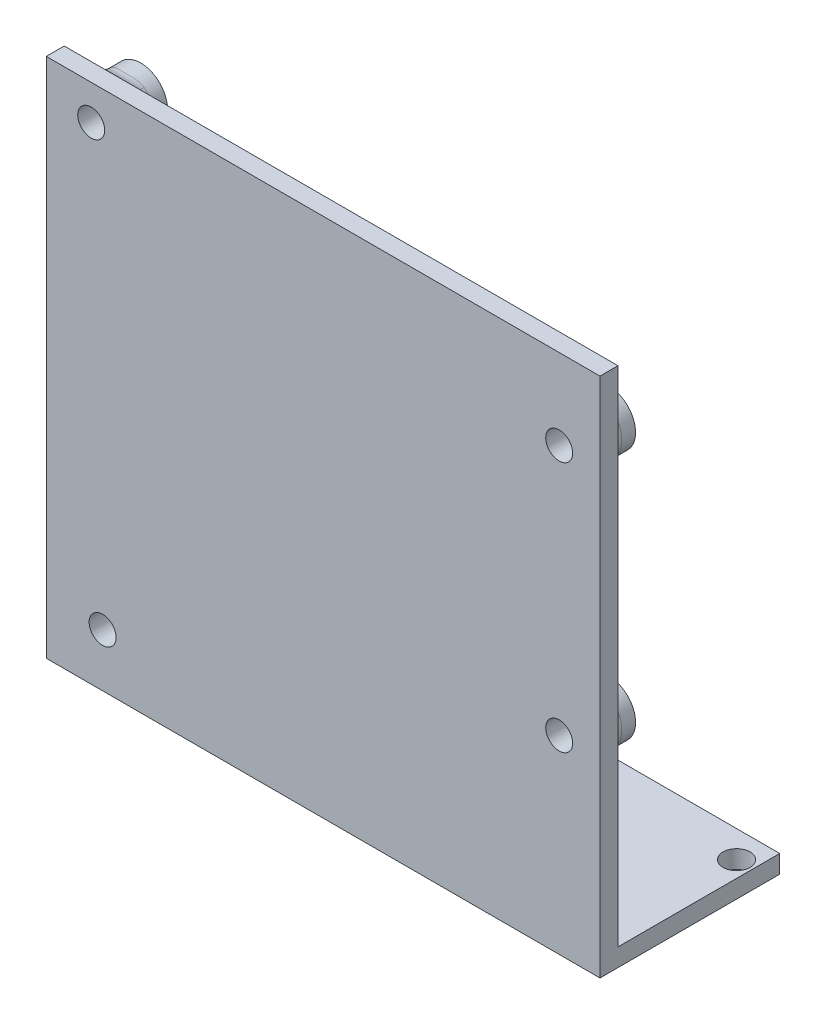
SolidWorks part; units mm, degrees
ref_plane "Piano frontale" through (0, 0, 0) normal (0, 0, 1) x (1, 0, 0)
ref_plane "Piano superiore" through (0, 0, 0) normal (0, 1, 0) x (1, 0, 0)
ref_plane "Piano destro" through (0, 0, 0) normal (1, 0, 0) x (0, 0, -1)
sketch "Schizzo1" plane through (0, 0, 0) normal (0, 0, 1) x (1, 0, 0)
  line L1 (87, 28) -> (-87, 28)
  line L2 (87, 28) -> (87, -28)
  line L3 (87, -28) -> (-87, -28)
  line L4 (-87, 28) -> (-87, -28)
  line L5 (87, 28) -> (-87, -28) construction
  line L6 (87, -28) -> (-87, 28) construction
  point P0 (0, 0)
  dimension "D1" = 56
  dimension "D2" = 174
extrude "Estrusione-Estrusione1" add sketch "Schizzo1" along normal blind 2
sketch "Schizzo4" plane through (0, 0, 0) normal (0, 0, -1) x (-1, 0, 0)
  line L0 (87, 0) -> (-87, 0) construction
  line L1 (87, 28) -> (87, -28) construction
  line L2 (-87, -28) -> (-87, 28) construction
  line L3 (83.5, 0) -> (83.5, -24.5) construction
  line L4 (83.5, -24.5) -> (25.5, -24.5) construction
  line L5 (83.5, 0) -> (83.5, 24.5) construction
  line L6 (83.5, 24.5) -> (25.5, 24.5) construction
  line L7 (25.5, 24.5) -> (25.5, -24.5) construction
  circle A0 centre (83.5, -24.5) radius 1.5
  circle A1 centre (25.5, -24.5) radius 1.5
  circle A2 centre (25.5, 24.5) radius 1.5
  circle A3 centre (83.5, 24.5) radius 1.5
  circle A4 centre (83.5, -24.5) radius 3
  circle A5 centre (25.5, -24.5) radius 3
  circle A6 centre (25.5, 24.5) radius 3
  circle A7 centre (83.5, 24.5) radius 3
  dimension "D5" = 3
  dimension "D6" = 3
  dimension "D7" = 3
  dimension "D8" = 3
  dimension "D9" = 6
  dimension "D10" = 6
  dimension "D11" = 6
  dimension "D12" = 6
  dimension "D1" = 3.5
  dimension "D2" = 24.5
  dimension "D3" = 58
  dimension "D4" = 24.5
extrude "Estrusione-Estrusione4" add sketch "Schizzo4" along normal blind 3.5
sketch "Schizzo5" plane through (0, 0, 0) normal (0, 0, -1) x (-1, 0, 0)
  circle A0 centre (83.5, -24.5) radius 1.5
  circle A1 centre (25.5, -24.5) radius 1.5
  circle A2 centre (25.5, 24.5) radius 1.5
  circle A3 centre (83.5, 24.5) radius 1.5
extrude "Taglio-Estrusione1" cut sketch "Schizzo5" against normal blind 2
sketch "Schizzo6" plane through (0, 0, 0) normal (0, 0, -1) x (-1, 0, 0)
  line L0 (-87, 0) -> (0, 0) construction
  line L1 (-87, -28) -> (-87, 28) construction
  line L2 (-87, -24.1216) -> (-87, 24.1216)
  line L3 (-87, -24.1216) -> (-31.6596, -24.1216) construction
  line L4 (-87, 24.1216) -> (-30.39, 24.1216) construction
  line L5 (-87, 19.0416) -> (-82.46, 19.0416) construction
  line L6 (-87, -8.8984) -> (-82.46, -8.8984) construction
  circle A0 centre (-30.39, 24.1216) radius 1.5
  circle A1 centre (-31.6596, -24.1216) radius 1.5
  circle A2 centre (-82.46, -8.8984) radius 1.5
  circle A3 centre (-82.46, 19.0416) radius 1.5
  circle A4 centre (-30.39, 24.1216) radius 3
  circle A5 centre (-31.6596, -24.1216) radius 3
  circle A6 centre (-82.46, 19.0416) radius 3
  circle A7 centre (-82.46, -8.8984) radius 3
  point P8 (-87, 0)
  dimension "D9" = 3
  dimension "D10" = 3
  dimension "D11" = 3
  dimension "D12" = 3
  dimension "D13" = 6
  dimension "D14" = 6
  dimension "D15" = 6
  dimension "D16" = 6
  dimension "D1" = 48.2433
  dimension "D2" = 0
  dimension "D3" = 55.3404
  dimension "D4" = 56.61
  dimension "D5" = 4.54
  dimension "D6" = 4.54
  dimension "D7" = 15.2233
  dimension "D8" = 5.08
extrude "Estrusione-Estrusione5" add sketch "Schizzo6" along normal blind 3.5 contours A7 | A2 | A6 | A3 | A4 | A0 | A5 | A1
sketch "Schizzo7" plane through (0, 0, 0) normal (0, 0, -1) x (-1, 0, 0)
  circle A0 centre (-82.46, 19.0416) radius 1.5
  circle A1 centre (-30.39, 24.1216) radius 1.5
  circle A2 centre (-31.6596, -24.1216) radius 1.5
  circle A3 centre (-82.46, -8.8984) radius 1.5
extrude "Taglio-Estrusione2" cut sketch "Schizzo7" against normal blind 2
fillet "Raccordo1" radius 2 8 edges at (-86.5, 24.5, 0) (-86.5, -24.5, 0) (-28.5, 24.5, 0) (-28.5, -24.5, 0) (27.39, 24.1216, 0) (28.6596, -24.1216, 0) (79.46, -8.8984, 0) (79.46, 19.0416, 0)
sketch "Schizzo8" plane through (0, 0, 0) normal (0, 0, -1) x (-1, 0, 0)
  line L0 (-25.39, 24.1216) -> (-25.39, 28) construction
  line L1 (-27.2343, 28) -> (21.9293, 28) construction
  line L2 (-25.39, 28) -> (-25.39, -28)
  line L3 (21.9293, -28) -> (-28.5039, -28) construction
  line L4 (-25.39, -28) -> (87.3118, -28)
  line L5 (87.3118, -28) -> (87.3118, 28.0874)
  line L6 (87.3118, 28.0874) -> (-25.39, 28)
  arc A0 (-33.5457, 28) -> (-27.2343, 28) centre (-30.39, 24.1216) ccw construction
extrude "Taglio-Estrusione3" cut sketch "Schizzo8" against normal blind 10 body kept at (87, -10.9932, 0)
sketch "Schizzo12" plane through (0, 0, 2) normal (0, 0, 1) x (1, 0, 0)
  line L0 (87, -28) -> (87, -30)
  line L1 (25.39, -28) -> (25.39, -30)
  line L2 (25.39, -30) -> (87, -30)
  line L3 (25.39, -28) -> (87, -28)
  dimension "D1" = 2
extrude "Estrusione-Estrusione7" add sketch "Schizzo12" against normal blind 20
sketch "Schizzo14" plane through (0, -28, 0) normal (0, 1, 0) x (1, 0, 0)
  line L0 (56.195, 18) -> (56.195, 0) construction
  line L1 (87, 18) -> (25.39, 18) construction
  line L2 (87, 0) -> (33.5457, 0) construction
  line L3 (56.195, 15) -> (87, 15) construction
  line L4 (87, 18) -> (87, 0) construction
  line L5 (56.195, 0) -> (87, 0) construction
  circle A0 centre (85.195, 15) radius 1.5
  circle A1 centre (27.195, 15) radius 1.5
  dimension "D2" = 3
  dimension "D3" = 29
  dimension "D1" = 15
extrude "Taglio-Estrusione5" cut sketch "Schizzo14" against normal blind 20
